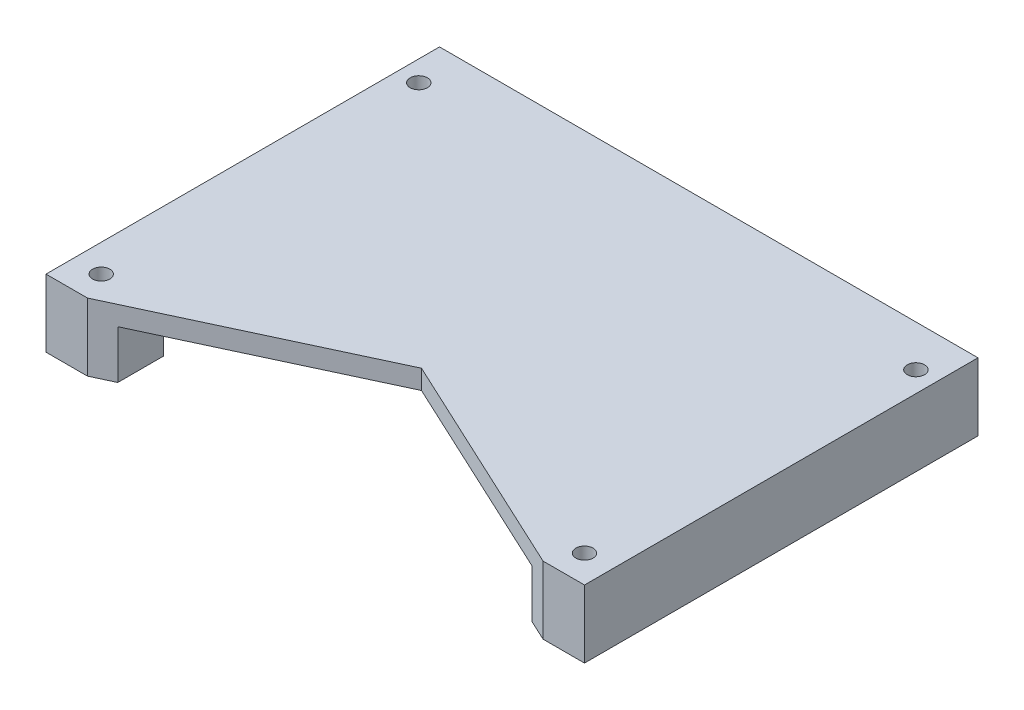
SolidWorks part; units mm, degrees
ref_plane "Front Plane" through (0, 0, 0) normal (0, 0, 1) x (1, 0, 0)
ref_plane "Top Plane" through (0, 0, 0) normal (0, 1, 0) x (1, 0, 0)
ref_plane "Right Plane" through (0, 0, 0) normal (1, 0, 0) x (0, 0, -1)
sketch "Sketch1" plane through (0, 0, 0) normal (0, 1, 0) x (1, 0, 0)
  line L1 (0, 0) -> (78, 0)
  line L2 (0, 0) -> (0, 57)
  line L3 (0, 57) -> (78, 57)
  line L4 (78, 0) -> (78, 57)
  dimension "D1" = 57
  dimension "D2" = 78
extrude "Boss-Extrude1" add sketch "Sketch1" along normal blind 9.8
sketch "Sketch2" plane through (0, 0, 0) normal (0, -1, 0) x (1, 0, 0)
  line L0 (78, -57) -> (0, -57) construction
  line L1 (6, -57) -> (72, -57)
  line L2 (6, -57) -> (6, -8)
  line L3 (6, -8) -> (72, -8)
  line L4 (72, -57) -> (72, -8)
  line L5 (0, -57) -> (0, 0) construction
  line L6 (78, 0) -> (78, -57) construction
  dimension "D1" = 6
  dimension "D2" = 6
  dimension "D3" = 49
extrude "Cut-Extrude1" cut sketch "Sketch2" against normal blind 7
sketch "Sketch3" plane through (0, 0, 0) normal (0, -1, 0) x (1, 0, 0)
  line L0 (72, -8) -> (6, -8) construction
  line L1 (9, -8) -> (69, -8)
  line L2 (9, -8) -> (9, 0)
  line L3 (9, 0) -> (69, 0)
  line L4 (69, -8) -> (69, 0)
  line L5 (0, 0) -> (78, 0) construction
  line L6 (0, -57) -> (0, 0) construction
  line L7 (78, 0) -> (78, -57) construction
  dimension "D1" = 9
  dimension "D2" = 9
extrude "Cut-Extrude2" cut sketch "Sketch3" against normal up to surface (7 mm away) up to face at (39, 7, -32.5)
sketch "Sketch4" plane through (0, 9.8, 0) normal (0, 1, 0) x (1, 0, 0)
  line L0 (0, 0) -> (78, 0) construction
  line L1 (6, 0) -> (39, 15.3882)
  line L2 (39, 15.3882) -> (72, 0)
  line L3 (39, 15.3882) -> (39, 57) construction
  line L4 (72, 0) -> (6, 0)
  line L5 (78, 57) -> (0, 57) construction
  dimension "D1" = 130
  dimension "D2" = 6
extrude "Cut-Extrude3" cut sketch "Sketch4" against normal up to next
hole_wizard "Tap Drill for M3 Tap1" positions "Sketch6" profile "Sketch5" hole size "M3" standard "ISO" end condition up to next
sketch "Sketch6" plane through (0, 0, 0) normal (0, -1, 0) x (-1, 0, 0)
  line L0 (-78, 57) -> (-72, 57) construction
  line L1 (-6, 57) -> (0, 57) construction
  line L2 (-72, 0) -> (-78, 0) construction
  line L3 (-78, 0) -> (-78, 57) construction
  line L5 (0, 57) -> (0, 0) construction
  point P0 (-4, 4)
  point P2 (-3, 51)
  point P4 (-74, 4)
  point P6 (-75, 51)
  dimension "D1" = 6
  dimension "D2" = 6
  dimension "D3" = 4
  dimension "D4" = 4
  dimension "D5" = 4
  dimension "D6" = 3
  dimension "D7" = 3
sketch "Sketch5" plane through (4, 0, -4) normal (1, 0, 0) x (0, 0, -1)
  line L0 (0, 0) -> (0, 9.8)
  line L1 (0, 9.8) -> (1.25, 9.8)
  line L2 (1.25, 9.8) -> (1.25, 0)
  line L5 (1.25, 0) -> (0, 0)
  line L11 (0, -6.35) -> (0, 107.95) construction
  dimension "Thru Hole Dia." = 2.5
  dimension "Thru Hole Depth" = 9.8
